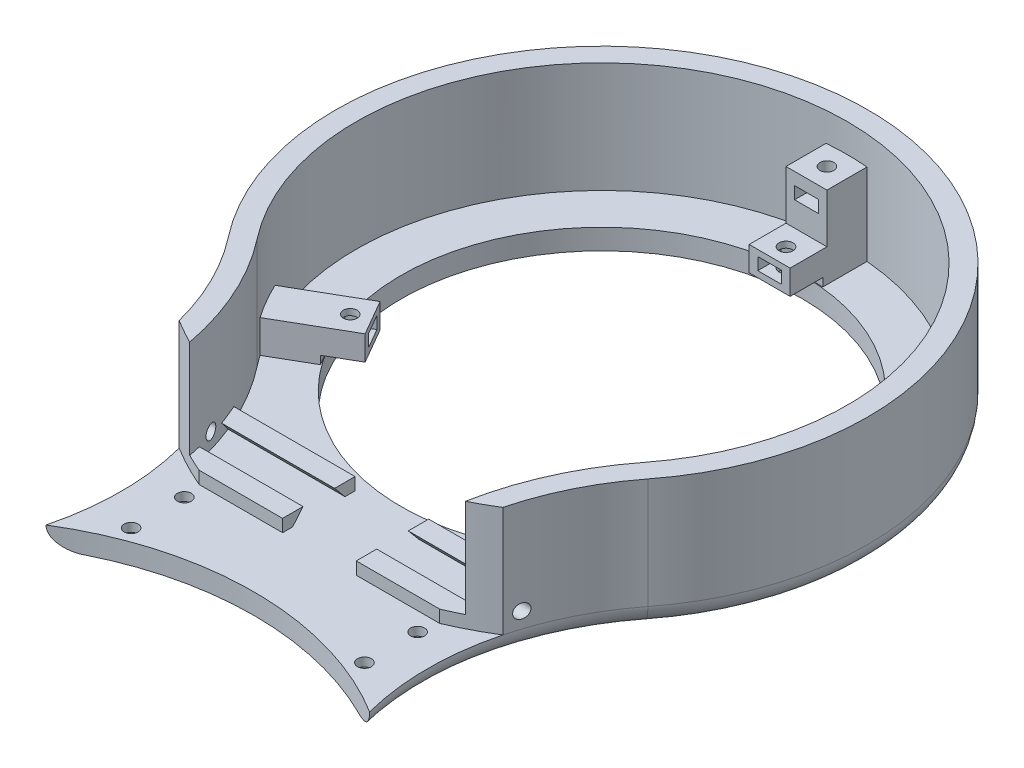
SolidWorks part; units mm, degrees
material "PLA"
ref_plane "Alzado" through (0, 0, 0) normal (0, 0, 1) x (1, 0, 0)
ref_plane "Planta" through (0, 0, 0) normal (0, 1, 0) x (1, 0, 0)
ref_plane "Vista lateral" through (0, 0, 0) normal (1, 0, 0) x (0, 0, -1)
sketch "Croquis1" plane through (0, 0, 0) normal (0, 1, 0) x (1, 0, 0)
  line L0 (0, 80) -> (0, -80) construction
  arc A0 (51.2348, 40) -> (-51.2348, 40) centre (0, 80) ccw
  arc A1 (-51.2348, -40) -> (51.2348, -40) centre (0, -80) ccw
  arc A2 (-51.2348, -40) -> (-51.2348, 40) centre (-102.4695, 0) ccw
  arc A3 (51.2348, 40) -> (51.2348, -40) centre (102.4695, 0) ccw
  point P8 (0, 0)
  dimension "D1" = 130
  dimension "D2" = 160
extrude "Saliente-Extruir1" add sketch "Croquis1" along normal blind 32
sketch "Croquis2" plane through (0, 32, 0) normal (0, 1, 0) x (1, 0, 0)
  arc A0 (47.2936, 43.0769) -> (-47.2936, 43.0769) centre (0, 80) ccw
  arc A1 (-47.2936, -43.0769) -> (47.2936, -43.0769) centre (0, -80) ccw
  arc A2 (-47.2936, -43.0769) -> (-47.2936, 43.0769) centre (-102.4695, 0) ccw
  arc A3 (47.2936, 43.0769) -> (47.2936, -43.0769) centre (102.4695, 0) ccw
  arc A4 (51.2348, 40) -> (-51.2348, 40) centre (0, 80) ccw construction
  arc A5 (-51.2348, -40) -> (51.2348, -40) centre (0, -80) ccw construction
  arc A6 (-51.2348, -40) -> (-51.2348, 40) centre (-102.4695, 0) ccw construction
  arc A7 (51.2348, 40) -> (51.2348, -40) centre (102.4695, 0) ccw construction
  dimension "D1" = 120
extrude "Cortar-Extruir1" cut sketch "Croquis2" against normal blind 27
sketch "Croquis3" plane through (0, 32, 0) normal (0, 1, 0) x (1, 0, 0)
  circle A0 centre (0, -80) radius 62.5
  dimension "D1" = 125
extrude "Cortar-Extruir2" cut sketch "Croquis3" against normal blind 29
sketch "Croquis4" plane through (0, 3, 0) normal (0, 1, 0) x (1, 0, 0)
  circle A0 centre (0, -80) radius 18
  circle A1 centre (0, -80) radius 62.5 construction
  dimension "D1" = 36
extrude "Saliente-Extruir2" add sketch "Croquis4" along normal blind 8
sketch "Croquis5" plane through (0, 0, 0) normal (0, -1, 0) x (1, 0, 0)
  circle A0 centre (0, -80) radius 49
  arc A1 (-51.2348, -40) -> (51.2348, -40) centre (0, -80) ccw construction
  dimension "D1" = 98
extrude "Cortar-Extruir3" cut sketch "Croquis5" against normal blind 5 contours A0
sketch "Croquis6" plane through (0, 5, 0) normal (0, 1, 0) x (1, 0, 0)
  arc A1 (-33.6854, 12.9904) -> (33.6854, 12.9904) centre (0, 80) ccw
  arc A3 (33.6854, 12.9904) -> (33.6854, -12.9904) centre (102.4695, 0) ccw
  arc A5 (47.2936, 43.0769) -> (40.3529, -32.2727) centre (102.4695, 0) ccw construction
  arc A7 (-33.6854, -12.9904) -> (-33.6854, 12.9904) centre (-102.4695, 0) ccw
  arc A8 (33.6854, -12.9904) -> (-33.6854, -12.9904) centre (0, -80) ccw
  arc A10 (-40.3529, -32.2727) -> (-47.2936, 43.0769) centre (-102.4695, 0) ccw construction
  dimension "D1" = 75
extrude "Saliente-Extruir3" add sketch "Croquis6" along normal blind 5
ref_axis "Eje1" through (0, 16.458, 80) along (0, -1, 0)
ref_plane "Plano1" through (9, 0, 0) normal (1, 0, 0) x (0, 0, -1)
sketch "Croquis7" plane through (9, 0, 0) normal (1, 0, 0) x (0, 0, -1)
  line L0 (11, 8.039) -> (11, 5)
  line L1 (11, 5) -> (13.45, 5)
  line L2 (13.45, 5) -> (16, 8.039)
  line L3 (16, 8.039) -> (11, 8.039)
  line L4 (23.7, 8.039) -> (28.7, 8.039)
  line L5 (28.7, 8.039) -> (28.7, 5)
  line L6 (28.7, 5) -> (26.25, 5)
  line L7 (26.25, 5) -> (23.7, 8.039)
  line L8 (-80, 16.458) -> (-80, -32.6754) construction
  line L10 (129, 5) -> (31, 5) construction
  dimension "D1" = 7.7
  dimension "D2" = 12.8
  dimension "D3" = 5
  dimension "D4" = 50
  dimension "D5" = 91
extrude "Saliente-Extruir4" add sketch "Croquis7" along normal up to surface (24.7738 mm away) up to face at (36.9068, 13, -2.8996)
mirror "Simetría1" about plane through (0, 0, 0) normal (1, 0, 0) of "Saliente-Extruir4"
sketch "Croquis8" plane through (0, 0, 0) normal (1, 0, 0) x (0, 0, -1)
  line L0 (121, 13) -> (141, 13)
  line L1 (141, 13) -> (141, 5)
  line L2 (141, 5) -> (129, 5)
  line L3 (129, 5) -> (129, 7)
  line L4 (129, 7) -> (121, 7)
  line L5 (121, 7) -> (121, 13)
  line L7 (129, 5) -> (31, 5) construction
  line L8 (129, 0) -> (129, 5) construction
  dimension "D1" = 20
  dimension "D2" = 6
  dimension "D3" = 2
  dimension "D4" = 8
extrude "Saliente-Extruir5" add sketch "Croquis8" along normal blind 5 and the other way blind 5
sketch "Croquis9" plane through (0, 13, 0) normal (0, 1, 0) x (1, 0, 0)
  line L0 (5, 121) -> (-5, 129) construction
  line L1 (-5, 139.7913) -> (-5, 121) construction
  line L2 (-5, 121) -> (5, 121) construction
  circle A0 centre (0, 125) radius 1.7
  point P15 (0, 121)
  dimension "D1" = 3.4
extrude "Cortar-Extruir4" cut sketch "Croquis9" against normal blind 8
ref_plane "Plano2" through (0, 10, 0) normal (0, 1, 0) x (1, 0, 0)
sketch "Croquis10" plane through (0, 10, 0) normal (0, 1, 0) x (1, 0, 0)
  line L0 (-2.9012, 123.325) -> (-2.9012, 116.675)
  line L1 (0, 121.65) -> (2.9012, 123.325) construction
  line L2 (2.9012, 123.325) -> (2.9012, 126.675)
  line L3 (2.9012, 126.675) -> (0, 128.35)
  line L4 (0, 128.35) -> (-2.9012, 126.675)
  line L5 (-2.9012, 126.675) -> (-2.9012, 123.325)
  line L6 (-2.9012, 123.325) -> (0, 121.65) construction
  line L7 (-2.9012, 116.675) -> (2.9012, 116.675)
  line L8 (2.9012, 116.675) -> (2.9012, 123.325)
  line L9 (-5, 139.7913) -> (-5, 121) construction
  circle A0 centre (0, 125) radius 3.35 construction
  dimension "D1" = 6.7
  dimension "D2" = 10
extrude "Cortar-Extruir5" cut sketch "Croquis10" against normal blind 1.5 and the other way blind 1.5
pattern_circular "MatrizC1" count 3 over 360 about axis through (0, 5, -80) along (0, -1, 0) of "Saliente-Extruir5", "Cortar-Extruir4", "Cortar-Extruir5"
sketch "Croquis11" plane through (0, 13, 0) normal (0, 1, 0) x (1, 0, 0)
  line L0 (-5, 139.7913) -> (-5, 121) construction
  line L1 (5, 130) -> (-5, 130)
  line L2 (5, 130) -> (5, 139.7913)
  line L4 (-5, 130) -> (-5, 139.7913)
  line L7 (5, 129) -> (5, 139.7913) construction
  line L8 (-5, 121) -> (5, 121) construction
  arc A0 (5, 139.7913) -> (-5, 139.7913) centre (0, 80) ccw
  arc A1 (47.2936, 43.0769) -> (-47.2936, 43.0769) centre (0, 80) ccw construction
  dimension "D1" = 9
extrude "Saliente-Extruir6" add sketch "Croquis11" along normal blind 12
sketch "Croquis12" plane through (0, 25, 0) normal (0, 1, 0) x (1, 0, 0)
  line L0 (-5, 130) -> (5, 130) construction
  circle A0 centre (0, 135) radius 1.7
  point P5 (0, 130)
  dimension "D1" = 3.4
  dimension "D2" = 5
extrude "Cortar-Extruir6" cut sketch "Croquis12" against normal blind 12
ref_plane "Plano3" through (0, 20.5, 0) normal (0, 1, 0) x (1, 0, 0)
sketch "Croquis13" plane through (0, 20.5, 0) normal (0, 1, 0) x (1, 0, 0)
  line L0 (-2.9012, 133.325) -> (-2.9012, 126.675)
  line L1 (0, 131.65) -> (2.9012, 133.325) construction
  line L2 (2.9012, 133.325) -> (2.9012, 136.675)
  line L3 (2.9012, 136.675) -> (0, 138.35)
  line L4 (0, 138.35) -> (-2.9012, 136.675)
  line L5 (-2.9012, 136.675) -> (-2.9012, 133.325)
  line L6 (-2.9012, 133.325) -> (0, 131.65) construction
  line L7 (-2.9012, 126.675) -> (2.9012, 126.675)
  line L8 (2.9012, 126.675) -> (2.9012, 133.325)
  line L9 (-5, 139.7913) -> (-5, 130) construction
  circle A0 centre (0, 135) radius 3.35 construction
  dimension "D2" = 6.7
  dimension "D1" = 10
extrude "Cortar-Extruir7" cut sketch "Croquis13" against normal blind 1.5 and the other way blind 1.5
sketch "Croquis14" plane through (0, 0, 0) normal (1, 0, 0) x (0, 0, -1)
  line L0 (16, 8.039) -> (19.85, 8.8) construction
  line L1 (19.85, 8.8) -> (23.7, 8.039) construction
  circle A0 centre (19.85, 8.8) radius 1.7
  dimension "D2" = 3.4
  dimension "D1" = 8.8
extrude "Cortar-Extruir8" cut sketch "Croquis14" against normal blind 58.5 and the other way blind 58
sketch "Croquis15" plane through (0, 0, 0) normal (0, -1, 0) x (1, 0, 0)
  line L1 (28.5, -6.5) -> (-28.5, -6.5) construction
  line L2 (28.5, -6.5) -> (28.5, 6.5) construction
  line L3 (28.5, 6.5) -> (-28.5, 6.5) construction
  line L4 (-28.5, -6.5) -> (-28.5, 6.5) construction
  line L5 (28.5, -6.5) -> (-28.5, 6.5) construction
  line L6 (28.5, 6.5) -> (-28.5, -6.5) construction
  circle A0 centre (-28.5, 6.5) radius 1.7
  circle A1 centre (-28.5, -6.5) radius 1.7
  circle A2 centre (28.5, 6.5) radius 1.7
  circle A3 centre (28.5, -6.5) radius 1.7
  point P0 (0, 0)
  dimension "D3" = 3.4
  dimension "D1" = 57
  dimension "D2" = 13
extrude "Cortar-Extruir9" cut sketch "Croquis15" against normal blind 11.5
sketch "Croquis16" plane through (0, 0, 0) normal (0, -1, 0) x (1, 0, 0)
  circle A0 centre (-28.5, 6.5) radius 2.95
  circle A1 centre (-28.5, -6.5) radius 2.95
  circle A2 centre (28.5, 6.5) radius 2.95
  circle A3 centre (28.5, -6.5) radius 2.95
  dimension "D1" = 5.9
extrude "Cortar-Extruir10" cut sketch "Croquis16" against normal blind 2.9
fillet "Redondeo1" radius 5 4 edges at (-37.4695, 0, 0) (0, 0, 145) (0, 0, -145) (37.4695, 0, 0)
sketch "Croquis17" plane through (0, 0, 0) normal (0, -1, 0) x (1, 0, 0)
  circle A0 centre (0, 0) radius 4.2
  circle A2 centre (0, -134.5) radius 4.2
  dimension "D2" = 8.4
  dimension "D1" = 134.5
extrude "Cortar-Extruir11" cut sketch "Croquis17" against normal blind 1.1
sketch "Croquis18" plane through (0, 0, 0) normal (0, 0, 1) x (1, 0, 0)
  line L0 (-35, 27) -> (-35, 17)
  line L1 (-35, 17) -> (-25, 27)
  line L2 (-25, 27) -> (-35, 27)
  line L3 (25, 27) -> (35, 27)
  line L4 (35, 27) -> (35, 17)
  line L5 (35, 17) -> (25, 27)
  line L6 (-32.4695, 32) -> (-47.2936, 32) construction
  dimension "D1" = 50
  dimension "D2" = 10
  dimension "D3" = 45
  dimension "D4" = 5
  dimension "D5" = 25
extrude "Saliente-Extruir7" add sketch "Croquis18" along normal blind 3 and the other way blind 3
sketch "Croquis19" plane through (0, 0, 0) normal (0, -1, 0) x (1, 0, 0)
  circle A0 centre (0, 80) radius 75
  dimension "D1" = 150
extrude "Cortar-Extruir12" cut sketch "Croquis19" against normal blind 35
sketch "Croquis20" plane through (0, 32, 0) normal (0, 1, 0) x (1, 0, 0)
  line L0 (-50, 24.0983) -> (-50, -24.0983)
  line L1 (50, 24.0983) -> (50, -24.0983)
  arc A0 (50, -24.0983) -> (-50, -24.0983) centre (0, -80) ccw
  arc A1 (-50, 24.0983) -> (50, 24.0983) centre (0, 80) ccw
  arc A2 (33.6854, -12.9904) -> (-33.6854, -12.9904) centre (0, -80) ccw construction
  arc A3 (-33.6854, 12.9904) -> (33.6854, 12.9904) centre (0, 80) ccw construction
  dimension "D1" = 100
extrude "Cortar-Extruir13" cut sketch "Croquis20" against normal blind 27
